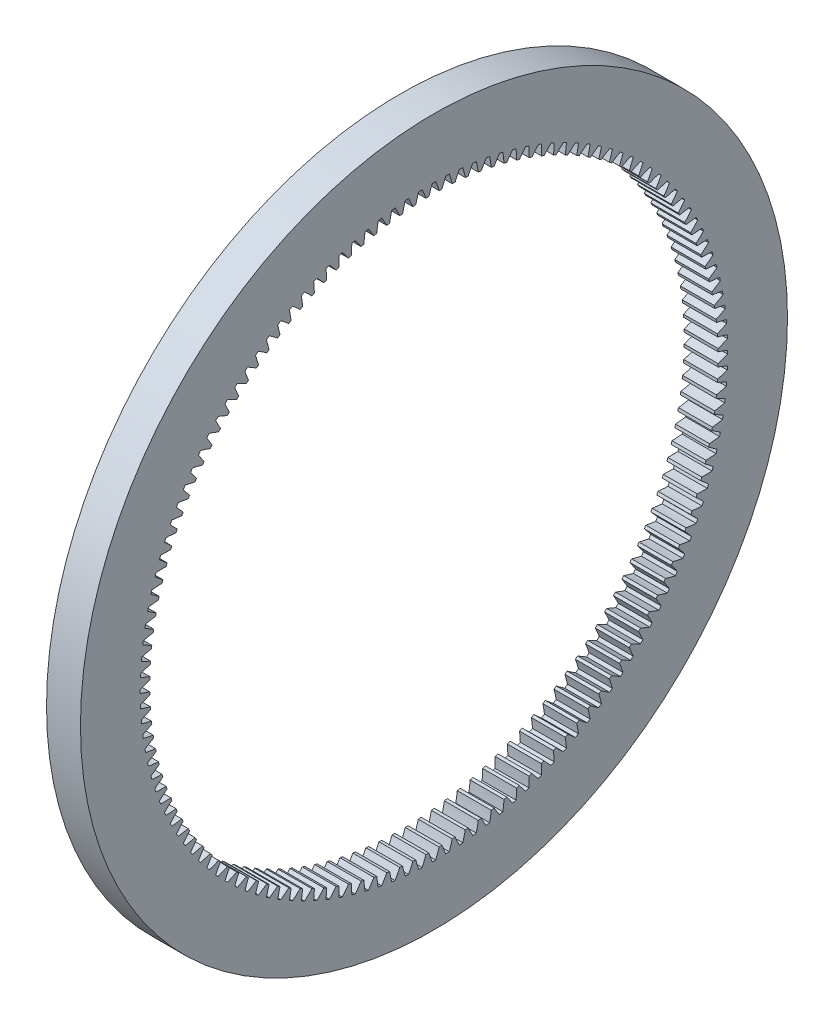
SolidWorks part; units mm, degrees
ref_plane "Plane1" through (0, 0, 0) normal (0, 0, 1) x (1, 0, 0)
ref_plane "Plane2" through (0, 0, 0) normal (0, 1, 0) x (1, 0, 0)
ref_plane "Plane3" through (0, 0, 0) normal (1, 0, 0) x (0, 0, -1)
sketch "HoldingSke" plane through (0, 0, 0) normal (0, 1, 0) x (1, 0, 0)
  line L0 (0, 0) -> (-0.4796, -0.4631)
  line L1 (-15, 0) -> (100, 0) construction
  line L2 (0, 0) -> (-2.1039, 2.3779)
  line L3 (0, 0) -> (-11.863, 4.5341)
  line L4 (0, 0) -> (-6.2122, 5.9991)
  line L5 (0, 0) -> (-23.7986, -8.8762)
  line L6 (0, 0) -> (-10.5278, -7.1032)
  line L7 (-2.1039, 2.3779) -> (3.3635, 27.1825)
  line L8 (-76.2, 3.8779) -> (-54.61, 3.8779)
  line L9 (-71.009, 38.7566) -> (-53.1078, 45.2721)
  line L10 (-76.2, 71.12) -> (104.1128, 71.12)
  line L11 (0, 0) -> (-12, 0)
  line L12 (-76.2, 101.6) -> (-76.147, 101.6)
  line L13 (24.9733, 27.94) -> (52.9518, 28.4284)
  line L14 (24.9733, 27.94) -> (24.9743, 27.94)
  line L15 (24.9733, 27.94) -> (100.4006, 29.5858)
  circle A0 centre (0, 0) radius 125
  circle A1 centre (0, 0) radius 12.7
  circle A2 centre (0, 0) radius 12.7
  dimension "Num_teeth" = 136
  dimension "Pitch_radius" = 180.3128
  dimension "Width" = 12
  dimension "Diameter" = 250
sketch "BasProSke" plane through (0, 0, 0) normal (0, 1, 0) x (1, 0, 0)
  line L0 (-10, 0) -> (60, 0) construction
  line L1 (0, 100.5) -> (0, 125)
  line L2 (0, 100.5) -> (12, 100.5)
  line L3 (12, 100.5) -> (12, 125)
  line L4 (12, 125) -> (0, 125)
  dimension "Thickness" = 12
  dimension "Diameter" = 250
revolve "Base-Revolve" add sketch "BasProSke" angle 360 about L0
sketch "TooCutSke" plane through (0, 0, 0) normal (1, 0, 0) x (0, 0, -1)
  line L3 (1.3106, 101.9916) -> (1.3106, 53.6633) construction
  line L4 (0, 0) -> (0, 59.563) construction
  line L5 (0, 0) -> (-1.5782, 68.3093) construction
  line L6 (-46.8474, 85.2044) -> (35.8402, 87.1149) construction
  circle A0 centre (0, 0) radius 102 construction
  circle A1 centre (0, 0) radius 103.876 construction
  circle A2 centre (0, 0) radius 86.2638 construction
  circle A3 centre (0, 0) radius 100.4746 construction
  arc A4 (1.818, 100.4582) -> (0.6125, 103.8742) centre (-46.8474, 85.2044) ccw
  arc A5 (1.818, 100.4582) -> (-1.818, 100.4582) centre (0, 0) ccw
  arc A6 (0.6125, 103.8742) -> (-0.6125, 103.8742) centre (0, 0) ccw
  arc A7 (-0.6125, 103.8742) -> (-1.818, 100.4582) centre (46.8474, 85.2044) ccw
extrude "ToothCut" cut sketch "TooCutSke" along normal through all
fillet "Breaks" [suppressed] radius 0.15
fillet "RootFillets" [suppressed] radius 0.376
pattern_circular "TeethCuts" count 136 every 2.647 about axis through (-10, 0, 0) along (1, 0, 0) of "RootFillets", "Breaks", "ToothCut"
equation "' \"Module@HoldingSke\" = 6.35"
equation "' \"Num_teeth@HoldingSke\" = 24"
equation "' \"Ap@HoldingSke\" =  14.5"
equation "' \"Ap@HoldingSke\" = 14.5"
equation "' \"Width@HoldingSke\" = 12"
equation "' \"Diameter@HoldingSke\" = 8 * 25.4"
equation "' \"Show_teeth@HoldingSke\" = 100"
equation "' \"Backlash@HoldingSke\" = 0.009 * 25.4"
equation "' \"Addendum_fac@HoldingSke\" = 1.0"
equation "' \"Dedendum_fac@HoldingSke\" = 1.25"
equation "' \"Dedendum_add@HoldingSke\" = 0.00005 * 25.4"
equation "' \"Clearance_fac@HoldingSke\" = 0.25"
equation "\"Pitch@HoldingSke\" = 1 / \"Module@HoldingSke\" "
equation "\"Overcut_dia@TooCutSke\" = (\"Num_teeth@HoldingSke\" - 2 * \"Addendum_fac@HoldingSke\") / \"Pitch@HoldingSke\" - 0.002 * 25.4"
equation "\"Pitch_dia@TooCutSke\" = \"Num_teeth@HoldingSke\" / \"Pitch@HoldingSke\""
equation "\"Base_dia@TooCutSke\" = \"Num_teeth@HoldingSke\" / \"Pitch@HoldingSke\" * cos((\"Ap@HoldingSke\"  * 3.14159265 / 180)) * 0.90"
equation "\"Root_dia@TooCutSke\" = \"Num_teeth@HoldingSke\"  / \"Pitch@HoldingSke\" + 2 *  \"Dedendum_fac@HoldingSke\"/ \"Pitch@HoldingSke\" + \"Dedendum_add@HoldingSke\" * 2"
equation "\"Half_ang@TooCutSke\" = 180 / \"Num_teeth@HoldingSke\""
equation "\"Half_CT@TooCutSke\" = \"Num_teeth@HoldingSke\" / \"Pitch@HoldingSke\" * sin((3.14159265 / 2 / \"Num_teeth@HoldingSke\")) / 2 + 10 * \"Backlash@HoldingSke\" / 4"
equation "\"Flank_rad@TooCutSke\" = \"Num_teeth@HoldingSke\" / \"Pitch@HoldingSke\" / 4"
equation "\"Radius@RootFillets\"= \"Clearance_fac@HoldingSke\" / \"Pitch@HoldingSke\" + \"Dedendum_add@HoldingSke\""
equation "\"Break_rad@Breaks\" = 0.02 / \"Pitch@HoldingSke\" * 5"
equation "\"Num_teeth@TeethCuts\" = int( \"Show_teeth@HoldingSke\" ) + 1"
equation "\"Num_teeth@TeethCuts\" = ((sgn( \"Num_teeth@TeethCuts\" - \"Num_teeth@HoldingSke\" )-1)*( \"Num_teeth@TeethCuts\" - \"Num_teeth@HoldingSke\" ))/-2+ \"Num_teeth@HoldingSke\""
equation "\"Num_teeth@TeethCuts\" = ((sgn( \"Num_teeth@TeethCuts\" - 2.0)+1)*( \"Num_teeth@TeethCuts\" - 2.0))/2 +2.0"
equation "\"Angle@TeethCuts\" = 360.0 / \"Num_teeth@HoldingSke\""
equation "\"Diameter@BasProSke\" = \"Num_teeth@HoldingSke\"  / \"Pitch@HoldingSke\" + 2 *  \"Dedendum_fac@HoldingSke\"/ \"Pitch@HoldingSke\" + \"Dedendum_add@HoldingSke\" * 2 + 0.002 * 25.4"
equation "\"Diameter@BasProSke\" = ((sgn( \"Diameter@BasProSke\"  - \"Diameter@HoldingSke\" )+1)*( \"Diameter@BasProSke\"  - \"Diameter@HoldingSke\" ))/2 + \"Diameter@HoldingSke\""
equation "\"Inside_diameter@BasProSke\" =  (\"Num_teeth@HoldingSke\" - 2 * \"Addendum_fac@HoldingSke\") / \"Pitch@HoldingSke\" "
equation "\"Thickness@BasProSke\"  = \"Width@HoldingSke\""
